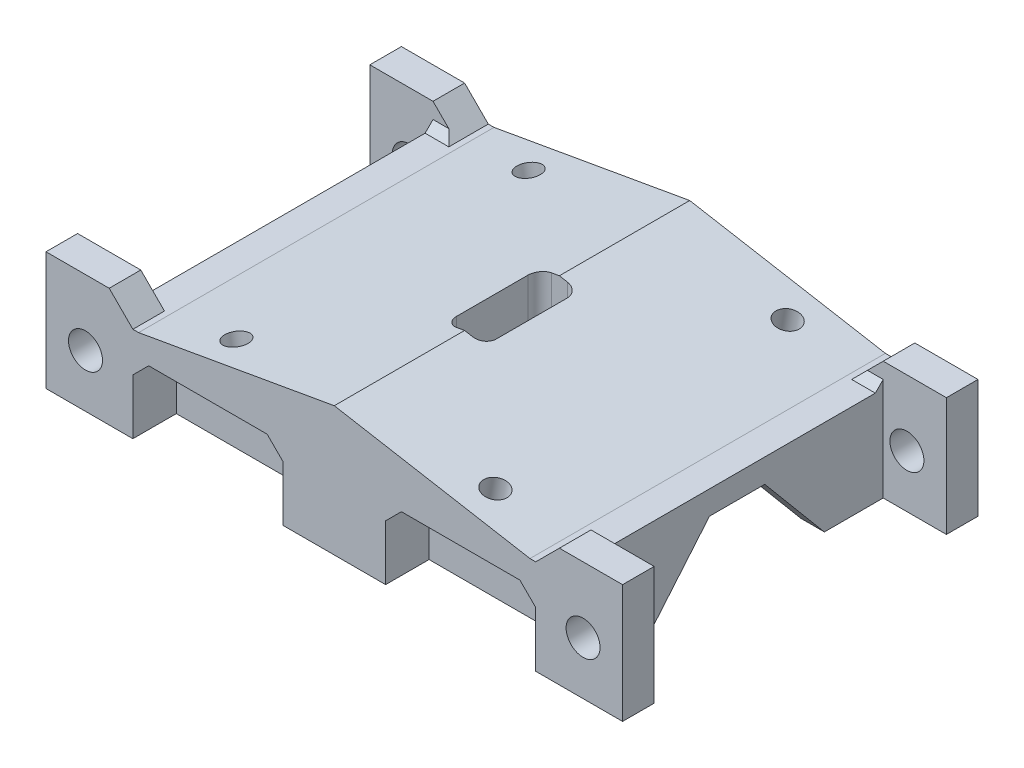
SolidWorks part; units mm, degrees
ref_plane "前视基准面" through (0, 0, 0) normal (0, 0, 1) x (1, 0, 0)
ref_plane "上视基准面" through (0, 0, 0) normal (0, 1, 0) x (1, 0, 0)
ref_plane "右视基准面" through (0, 0, 0) normal (1, 0, 0) x (0, 0, -1)
sketch "草图1" plane through (0, 0, 0) normal (0, 1, 0) x (1, 0, 0)
  line L1 (0, 0) -> (57, 0)
  line L2 (0, 0) -> (0, 45)
  line L3 (0, 45) -> (57, 45)
  line L4 (57, 0) -> (57, 45)
  dimension "D1" = 45
  dimension "D2" = 57
extrude "凸台-拉伸1" add sketch "草图1" along normal blind 3
sketch "草图2" plane through (0, 0, 0) normal (-1, 0, 0) x (0, 0, 1)
  line L0 (0, 6) -> (-4, 6)
  line L1 (-4, 6) -> (-4, -9)
  line L2 (-4, -9) -> (0, -9)
  line L3 (0, -9) -> (0, 6)
  line L4 (-45, 3) -> (0, 3) construction
  line L5 (-45, 0) -> (0, 0) construction
  line L8 (0, 3) -> (0, 0) construction
  dimension "D1" = 3
  dimension "D2" = 9
  dimension "D3" = 4
extrude "凸台-拉伸2" add sketch "草图2" along normal blind 8
sketch "草图3" plane through (57, 0, 0) normal (1, 0, 0) x (0, 0, -1)
  line L0 (0, 6) -> (0, -9)
  line L1 (0, -9) -> (4, -9)
  line L2 (4, -9) -> (4, 6)
  line L3 (4, 6) -> (0, 6)
extrude "凸台-拉伸3" add sketch "草图3" along normal blind 8
sketch "草图4" plane through (57, 0, 0) normal (-1, 0, 0) x (0, 0, 1)
  line L0 (-11.4481, -9) -> (-19, 0)
  line L1 (-4, 0) -> (-45, 0) construction
  line L2 (-19, 0) -> (0, 0)
  line L3 (0, 0) -> (0, -9)
  line L4 (0, -9) -> (-11.4481, -9)
  dimension "D1" = 50
  dimension "D2" = 19
extrude "凸台-拉伸4" add sketch "草图4" along normal blind 3
sketch "草图5" plane through (0, 0, 0) normal (1, 0, 0) x (0, 0, -1)
  line L0 (0, 0.3045) -> (0, -9)
  line L1 (0, -9) -> (11.4481, -9)
  line L2 (11.4481, -9) -> (19, 0)
  line L3 (45, 0) -> (4, 0) construction
  line L4 (19, 0) -> (0, 0)
  line L5 (11.4481, -9) -> (4, -9) construction
  line L6 (19, 0) -> (11.4481, -9) construction
  line M3 (4, -9) -> (4, 0)
  line M4 (4, 0) -> (0, 0)
  line M5 (0, 0) -> (0, -9)
  line M6 (0, -9) -> (4, -9)
  dimension "D1" = 50
extrude "凸台-拉伸5" add sketch "草图5" along normal blind 3 contours L2 L4 M3 | M6 M3 M4 M5 region at (0, -4.5, -2) region at (0, -3.9954, -9.8237)
chamfer "倒角1" distance 3 angle 45 2 edges at (0, 3, -2) (57, 3, -2)
sketch "草图6" plane through (0, 0, -4) normal (0, 0, -1) x (-1, 0, 0)
  line L0 (-60, -2.3233) -> (3, -2.3233) construction
  line L3 (-28.5, 0) -> (-28.5, 11.0492) construction
  line L4 (-57, 0) -> (0, 0) construction
  line L5 (-65, -9) -> (-57, -9) construction
  circle A0 centre (3, -2.3233) radius 2.15
  circle A1 centre (-60, -2.3233) radius 2.15
  dimension "D1" = 31.5
  dimension "D2" = 6.6767
  dimension "D3" = 4.3
extrude "切除-拉伸1" cut sketch "草图6" against normal blind 4
sketch "草图7" plane through (0, 3, 0) normal (0, 1, 0) x (1, 0, 0)
  line L0 (28, 49.7957) -> (28, -5.721) construction
  line L1 (8, 41) -> (8, 4)
  line L2 (3, 0) -> (54, 0) construction
  line L3 (0, 45) -> (0, 4) construction
  line L4 (48, 41) -> (48, 4)
  circle A0 centre (8, 41) radius 1.6
  circle A1 centre (8, 4) radius 1.6
  circle A2 centre (48, 4) radius 1.6
  circle A3 centre (48, 41) radius 1.6
  dimension "D1" = 37
  dimension "D2" = 4
  dimension "D3" = 8
extrude "切除-拉伸2" [suppressed] cut sketch "草图7" against normal blind 3 contours A3 | A2 | A0 | A1
sketch "草图8" plane through (0, 0, 0) normal (0, -1, 0) x (1, 0, 0)
  line L0 (24, -45) -> (32, -45)
  line L1 (57, -45) -> (0, -45) construction
  line L2 (32, -45) -> (32, -42)
  line L3 (32, -42) -> (24, -42)
  line L4 (24, -42) -> (24, -45)
  line L5 (28, 5.34) -> (28, -50.6665) construction
  line L6 (0, -45) -> (0, -19) construction
  point P10 (32, -43.5)
  dimension "D1" = 28
  dimension "D2" = 3
  dimension "D3" = 8
  dimension "D4" = 4
extrude "凸台-拉伸6" add sketch "草图8" along normal blind 9
sketch "草图9" plane through (32, 0, 0) normal (1, 0, 0) x (0, 0, -1)
  line L0 (45, 0) -> (29, 0)
  line L1 (29, 0) -> (35.3019, -9)
  line L2 (35.3019, -9) -> (45, -9)
  line L3 (45, -9) -> (45, 0)
  dimension "D1" = 55
  dimension "D2" = 16
extrude "凸台-拉伸7" add sketch "草图9" along normal blind 3
sketch "草图12" plane through (0, 3, 0) normal (0, 1, 0) x (1, 0, 0)
  line L0 (28.5, 45) -> (28.5, 0) construction
  line L1 (26, 28.5) -> (26, 16.5)
  line L2 (26, 16.5) -> (31, 16.5)
  line L3 (31, 16.5) -> (31, 28.5)
  line L4 (31, 28.5) -> (26, 28.5)
  line L5 (0, 45) -> (0, 4) construction
  line L6 (0, 22.5) -> (57, 22.5) construction
  line L7 (3, 0) -> (54, 0) construction
  line L8 (57, 4) -> (57, 45) construction
  line L9 (57, 45) -> (0, 45) construction
  line L10 (3, 0) -> (54, 0) construction
  dimension "D2" = 2.5
  dimension "D3" = 2.5
  dimension "D4" = 22.5
  dimension "D5" = 6
  dimension "D6" = 6
extrude "切除-拉伸4" cut sketch "草图12" against normal blind 3
fillet "圆角1" radius 1.5 4 edges at (31, 1.5, -16.5) (26, 1.5, -16.5) (26, 1.5, -28.5) (31, 1.5, -28.5)
ref_plane "基准面1" through (28.5, 0, 0) normal (1, 0, 0) x (0, 0, -1)
sketch "草图13" plane through (0, 3, 0) normal (0, 1, 0) x (1, 0, 0)
  line L0 (36, 45) -> (36, 0) construction
  line L1 (57, 45) -> (0, 45) construction
  line L2 (3, 0) -> (54, 0) construction
  line L3 (57, 4) -> (57, 45) construction
  dimension "D1" = 21
ref_plane "基准面2" through (34.4014, -6.0659, 0) normal (0.9848, -0.1736, 0) x (0, 0, 1)
sketch "草图14" plane through (34.4014, -6.0659, 0) normal (0.9848, -0.1736, 0) x (0, 0, 1)
  line L0 (-45, -9.2058) -> (0, -9.2058) construction
  line L1 (-45, -9.2058) -> (0, -9.2058) construction
  line L3 (-45, -9.2058) -> (0, -9.2058) construction
  line L4 (-45, -9.2058) -> (-45, -12.2058) construction
  line L5 (-45, -12.2058) -> (0, -12.2058) construction
  line L6 (0, -9.2058) -> (0, -12.2058) construction
  dimension "D1" = 3
ref_plane "基准面3" through (2.1195, 12.0203, 0) normal (0.1736, 0.9848, 0) x (0, 0, 1)
sketch "草图15" plane through (2.1195, 12.0203, 0) normal (0.1736, 0.9848, 0) x (0, 0, 1)
  line L1 (-45, 34.9321) -> (0, 34.9321)
  line L2 (-45, 34.9321) -> (-45, 52.6587)
  line L3 (-45, 52.6587) -> (0, 52.6587)
  line L4 (0, 34.9321) -> (0, 52.6587)
extrude "凸台-拉伸9" add sketch "草图15" against normal up to body separate body
sketch "草图16" plane through (2.1195, 12.0203, 0) normal (0.1736, 0.9848, 0) x (0.9848, -0.1736, 0)
  line L0 (43.4391, 45) -> (43.4391, 0) construction
  line L1 (51.946, 45) -> (34.9321, 45) construction
  line L2 (34.9321, 0) -> (51.946, 0) construction
  line L3 (51.946, 22.5) -> (43.4391, 22.5) construction
  line L4 (51.946, 45) -> (51.946, 0) construction
  circle A0 centre (43.4391, 41) radius 1.5
  circle A1 centre (43.4391, 4) radius 1.5
  dimension "D1" = 3
  dimension "D2" = 18.5
extrude "切除-拉伸5" cut sketch "草图16" against normal through all
mirror "镜向1" about plane through (28.5, 0, 0) normal (1, 0, 0) of "切除-拉伸5", "凸台-拉伸9"
ref_plane "基准面4" through (0, 0, -22.5) normal (0, 0, 1) x (1, 0, 0)
mirror "镜向2" about plane through (0, 0, -22.5) normal (0, 0, 1) of "凸台-拉伸4", "倒角1", "凸台-拉伸3", "凸台-拉伸2", "切除-拉伸1", "凸台-拉伸5"
chamfer "倒角2" distance 1 angle 45 2 edges at (1.5, 3, -41) (55.5, 3, -41)
chamfer "倒角3" distance 2 angle 45 5 edges at (54, 0, -9.5) (54, 0, -35.5) (3, 0, -35.5) (3, 0, -9.5) (35, 0, -37)
other "删除面1" face at (28.5, 3, -22.5) face at (20.7395, 4.4772, -22.5) face at (36.2605, 4.4772, -22.5) and patch yes
ref_plane "基准面5" through (28.5, 0, 0) normal (-1, 0, 0) x (0, 0, 1)
mirror "镜向3" about plane through (28.5, 0, 0) normal (-1, 0, 0) of "凸台-拉伸7"
sketch "草图20" plane through (0, -9, 0) normal (0, -1, 0) x (1, 0, 0)
  line L0 (3, -37.5) -> (25, -37.5)
  line L1 (3, -45) -> (3, 0) construction
  line L2 (54, 0) -> (54, -17.3218) construction
  line L3 (22, -45) -> (5, -45) construction
  line L5 (25, -42) -> (25, -29) construction
  line L8 (32, -35.3019) -> (32, -42) construction
  line L9 (32, -37.5) -> (54, -37.5)
  dimension "D1" = 7.5
extrude "拉伸-薄壁2" add sketch "草图20" against normal blind 10 thin thin type mid plane wall 4
mirror "镜向4" about plane through (0, 0, -22.5) normal (0, 0, 1) of "凸台-拉伸6", "镜向3", "拉伸-薄壁2"
sketch "草图21" plane through (0, -9, 0) normal (0, -1, 0) x (1, 0, 0)
  line L0 (13.5, -9.5) -> (13.5, -35.5)
  line L1 (5, -9.5) -> (22, -9.5) construction
  line L2 (5, -35.5) -> (22, -35.5) construction
extrude "拉伸-薄壁3" add sketch "草图21" against normal blind 10 thin thin type mid plane wall 4
mirror "镜向5" about plane through (28.5, 0, 0) normal (-1, 0, 0) of "拉伸-薄壁3"
chamfer "倒角4" distance 2 angle 45 6 edges at (35, 0, -12.75) (35, 0, -2.75) (22, 0, -2.75) (22, 0, -12.75) (22, 0, -42.25) (22, 0, -32.25)
